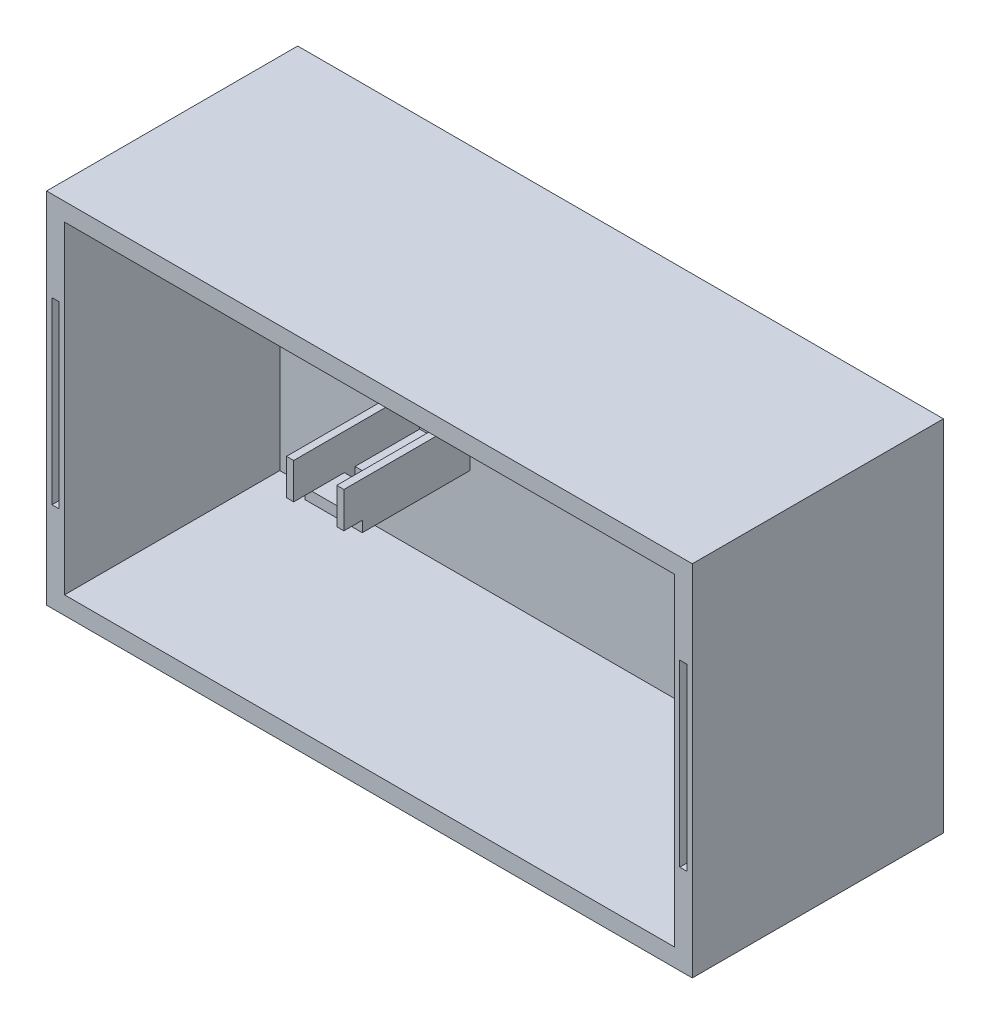
SolidWorks part; units mm, degrees
ref_plane "Piano frontale" through (0, 0, 0) normal (0, 0, 1) x (1, 0, 0)
ref_plane "Piano superiore" through (0, 0, 0) normal (0, 1, 0) x (1, 0, 0)
ref_plane "Piano destro" through (0, 0, 0) normal (1, 0, 0) x (0, 0, -1)
sketch "Schizzo1" plane through (0, 0, 0) normal (0, 1, 0) x (1, 0, 0)
  line L1 (0, 70) -> (180, 70)
  line L2 (0, 70) -> (0, 0)
  line L3 (0, 0) -> (180, 0)
  line L4 (180, 70) -> (180, 0)
  line L5 (0, 70) -> (180, 70)
  line L6 (0, 70) -> (0, 60)
  line L7 (0, 60) -> (180, 60)
  line L8 (180, 70) -> (180, 60)
  dimension "D1" = 180
  dimension "D2" = 70
  dimension "D3" = 10
extrude "Estrusione-Estrusione1" add sketch "Schizzo1" along normal blind 5 contours L7 L2 L3 L4 region at (90, 0, -30)
extrude "Estrusione-Estrusione2" add sketch "Schizzo1<3>" along normal blind 100 contours L2 L7 L4 L1 region at (90, 0, -65)
sketch "Schizzo1<3>" plane through (0, 0, 0) normal (0, 1, 0) x (1, 0, 0) same geometry as "Schizzo1"
sketch "Schizzo2" plane through (0, 0, -60) normal (0, 0, 1) x (1, 0, 0)
  line L0 (180, 100) -> (180, 5) construction
  line L1 (0, 100) -> (180, 100)
  line L2 (0, 100) -> (0, 95)
  line L3 (0, 95) -> (180, 95)
  line L4 (180, 100) -> (180, 95)
  dimension "D1" = 5
extrude "Estrusione-Estrusione3" add sketch "Schizzo2" along normal up to surface (60 mm away) up to face at (90, 2.5, 0)
sketch "Schizzo3" plane through (0, 0, -60) normal (0, 0, 1) x (1, 0, 0)
  line L0 (0, 5) -> (180, 5) construction
  line L1 (0, 95) -> (5, 95)
  line L2 (0, 95) -> (0, 5)
  line L3 (0, 5) -> (5, 5)
  line L4 (5, 95) -> (5, 5)
  line L5 (180, 95) -> (0, 95) construction
  line L6 (180, 5) -> (175, 5)
  line L7 (180, 5) -> (180, 95)
  line L8 (180, 95) -> (175, 95)
  line L9 (175, 5) -> (175, 95)
  dimension "D1" = 5
  dimension "D2" = 5
extrude "Estrusione-Estrusione4" add sketch "Schizzo3" along normal up to surface (60 mm away) up to face at (90, 97.5, 0)
sketch "Schizzo4" plane through (0, 5, 0) normal (0, 1, 0) x (1, 0, 0)
  line L0 (5, 60) -> (175, 60) construction
  line L1 (44, 42) -> (56, 42)
  line L2 (44, 42) -> (44, 39)
  line L3 (44, 39) -> (56, 39)
  line L4 (56, 42) -> (56, 39)
  line L5 (5, 0) -> (5, 60) construction
  point P6 (50, 39)
  dimension "D1" = 18
  dimension "D2" = 12
  dimension "D3" = 3
  dimension "D4" = 45
extrude "Taglio-Estrusione1" cut sketch "Schizzo4" against normal blind 90
sketch "Schizzo6" plane through (0, 5, 0) normal (0, 1, 0) x (1, 0, 0)
  line L0 (44, 42) -> (44, 39) construction
  line L1 (44, 34) -> (42, 34)
  line L2 (44, 34) -> (44, 49.5406)
  line L3 (44, 49.5406) -> (42, 49.5406)
  line L4 (42, 34) -> (42, 49.5406)
  line L5 (56, 34) -> (58, 34)
  line L6 (56, 34) -> (56, 49.5406)
  line L7 (56, 49.5406) -> (58, 49.5406)
  line L8 (58, 34) -> (58, 49.5406)
  line L9 (56, 39) -> (56, 42) construction
  dimension "D1" = 2
  dimension "D2" = 2
  dimension "D3" = 5
  dimension "D4" = 5
extrude "Estrusione-Estrusione5" add sketch "Schizzo6" along normal blind 10
sketch "Schizzo10" plane through (0, 0, -60) normal (0, 0, 1) x (1, 0, 0)
  line L2 (42, 34.5) -> (58, 34.5)
  line L3 (42, 34.5) -> (42, 31.5)
  line L4 (42, 31.5) -> (58, 31.5)
  line L5 (58, 34.5) -> (58, 31.5)
  line L6 (5, 5) -> (175, 5) construction
  line L7 (42, 15) -> (42, 5) construction
  line L8 (58, 15) -> (58, 5) construction
  dimension "D1" = 29.5
  dimension "D2" = 3
extrude "Estrusione-Estrusione7" add sketch "Schizzo10" along normal blind 30
sketch "Schizzo11" plane through (0, 31.5, 0) normal (0, -1, 0) x (1, 0, 0)
  line L1 (44, -39) -> (56, -39)
  line L2 (44, -39) -> (44, -42)
  line L3 (44, -42) -> (56, -42)
  line L4 (56, -39) -> (56, -42)
extrude "Taglio-Estrusione6" cut sketch "Schizzo11" against normal blind 5
sketch "Schizzo12" plane through (0, 0, -60) normal (0, 0, 1) x (1, 0, 0)
  line L0 (58, 34.5) -> (42, 34.5) construction
  line L1 (45.5, 60.5) -> (54.5, 60.5)
  line L2 (45.5, 60.5) -> (45.5, 57.5)
  line L3 (45.5, 57.5) -> (54.5, 57.5)
  line L4 (54.5, 60.5) -> (54.5, 57.5)
  line L5 (5, 95) -> (5, 5) construction
  point P6 (50, 57.5)
  dimension "D1" = 23
  dimension "D2" = 3
  dimension "D3" = 9
  dimension "D4" = 45
extrude "Taglio-Estrusione7" cut sketch "Schizzo12" against normal blind 20
sketch "Schizzo13" plane through (0, 34.5, 0) normal (0, 1, 0) x (1, 0, 0)
  line L0 (44, 39) -> (44, 42) construction
  line L1 (42, 60) -> (44, 60)
  line L2 (42, 60) -> (42, 24.8858)
  line L3 (42, 24.8858) -> (44, 24.8858)
  line L4 (44, 60) -> (44, 24.8858)
  line L5 (58, 60) -> (56, 60)
  line L6 (58, 60) -> (58, 24.8858)
  line L7 (58, 24.8858) -> (56, 24.8858)
  line L8 (56, 60) -> (56, 24.8858)
  line L9 (56, 42) -> (56, 39) construction
  line L10 (42, 30) -> (42, 60) construction
  line L12 (0, 70) -> (180, 70) construction
  dimension "D1" = 35.1142
  dimension "D2" = 10
  dimension "D3" = 2
extrude "Estrusione-Estrusione8" add sketch "Schizzo13" along normal blind 10
sketch "Schizzo15" plane through (0, 0, -34) normal (0, 0, 1) x (1, 0, 0)
  line L0 (5, 5) -> (175, 5) construction
  line L1 (38.3693, 16.9819) -> (60.2962, 16.9819)
  line L2 (38.3693, 16.9819) -> (38.3693, 5)
  line L3 (38.3693, 5) -> (60.2962, 5)
  line L4 (60.2962, 16.9819) -> (60.2962, 5)
extrude "Taglio-Estrusione8" cut sketch "Schizzo15" against normal up to next (26 mm away)
sketch "Schizzo16" plane through (0, 0, 0) normal (0, -1, 0) x (1, 0, 0)
  line L1 (44, -39) -> (56, -39)
  line L2 (44, -39) -> (44, -42)
  line L3 (44, -42) -> (56, -42)
  line L4 (56, -39) -> (56, -42)
extrude "Estrusione-Estrusione9" add sketch "Schizzo16" against normal up to surface (5 mm away) up to face at (50, 5, -40.5)
sketch "Schizzo17" plane through (0, 0, -60) normal (0, 0, 1) x (1, 0, 0)
  line L0 (56, 34.5) -> (44, 34.5) construction
  line L1 (56, 34.5) -> (44, 34.5) construction
  circle A0 centre (126, 50.9) radius 9.5
  point P6 (50, 34.5)
  dimension "D1" = 19
  dimension "D2" = 16.4
  dimension "D3" = 76
extrude "Taglio-Estrusione9" cut sketch "Schizzo17" against normal blind 6
sketch "Schizzo21" plane through (0, 0, 0) normal (0, 0, 1) x (1, 0, 0)
  line L0 (0, 100) -> (0, 0) construction
  line L1 (1.5, 75) -> (3.5, 75)
  line L2 (1.5, 75) -> (1.5, 25)
  line L3 (1.5, 25) -> (3.5, 25)
  line L4 (3.5, 75) -> (3.5, 25)
  line L5 (176.5, 75) -> (178.5, 75)
  line L6 (176.5, 75) -> (176.5, 25)
  line L7 (176.5, 25) -> (178.5, 25)
  line L8 (178.5, 75) -> (178.5, 25)
  line L9 (175, 95) -> (5, 95) construction
  line L10 (5, 5) -> (175, 5) construction
  line L11 (180, 100) -> (180, 0) construction
  dimension "D1" = 2
  dimension "D2" = 1.5
  dimension "D3" = 20
  dimension "D4" = 20
  dimension "D5" = 20
  dimension "D6" = 20
  dimension "D7" = 2
  dimension "D8" = 1.5
extrude "Taglio-Estrusione10" cut sketch "Schizzo21" against normal blind 2
